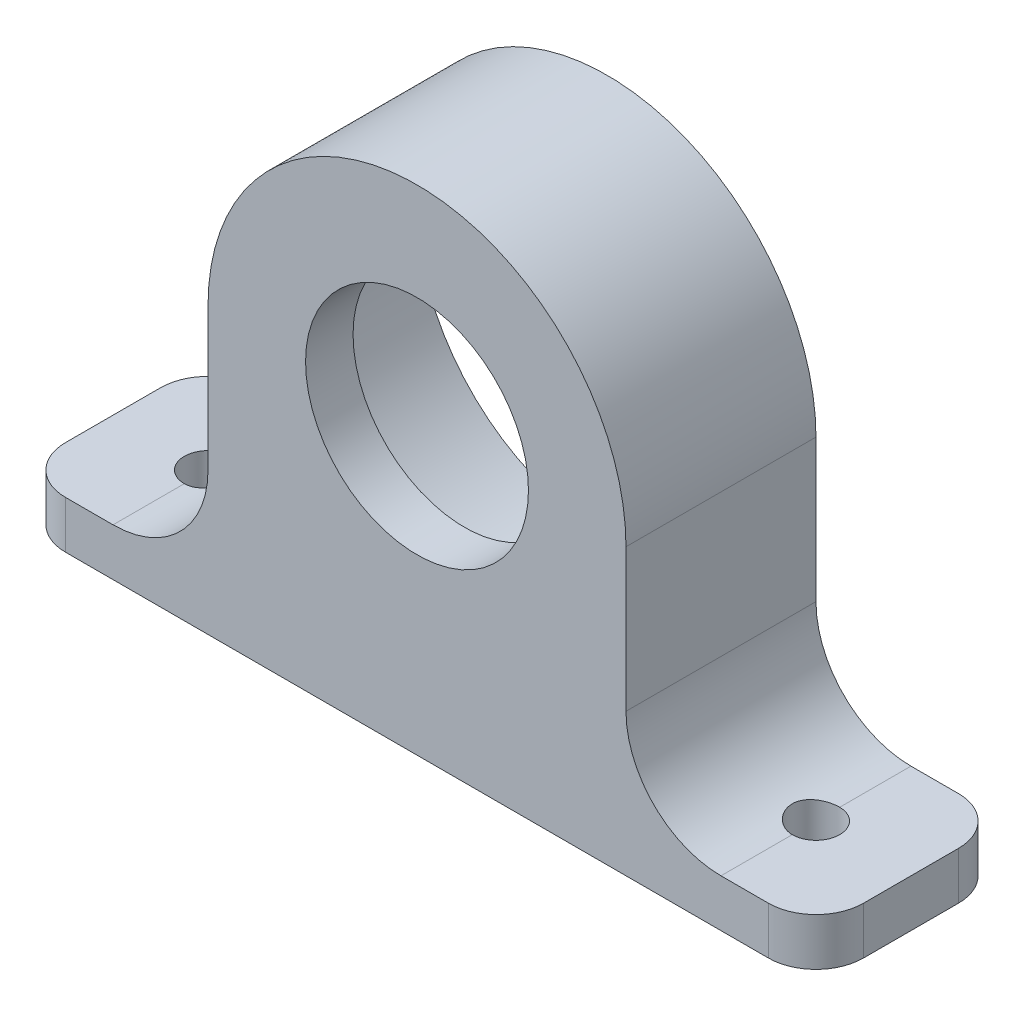
SolidWorks part; units mm, degrees
ref_plane "Plan de face" through (0, 0, 0) normal (0, 0, 1) x (1, 0, 0)
ref_plane "Plan de dessus" through (0, 0, 0) normal (0, 1, 0) x (1, 0, 0)
ref_plane "Plan de droite" through (0, 0, 0) normal (1, 0, 0) x (0, 0, -1)
sketch "Esquisse1" plane through (0, 0, 0) normal (0, 0, 1) x (1, 0, 0)
  line L0 (42, 0) -> (-42, 0)
  line L1 (-42, 0) -> (-42, 5)
  line L2 (-42, 5) -> (-22, 5)
  line L3 (-22, 5) -> (-22, 30)
  line L4 (0, 11.6708) -> (0, 4.3779) construction
  line L5 (42, 0) -> (42, 5)
  line L6 (42, 5) -> (22, 5)
  line L7 (22, 5) -> (22, 30)
  arc A2 (-22, 30) -> (22, 30) centre (0, 30) cw
  circle A3 centre (0, 30) radius 20
  point P12 (0, 0)
  dimension "D1" = 22
  dimension "D3" = 40
  dimension "D2" = 30
  dimension "D4" = 20
  dimension "D5" = 5
extrude "Boss.-Extru.1" add sketch "Esquisse1" along normal blind 20
sketch "Esquisse2" plane through (0, 5, 0) normal (0, 1, 0) x (1, 0, 0)
  line L0 (-42, -20) -> (-42, 0) construction
  line L2 (0, 8.854) -> (0, 0) construction
  circle A0 centre (-32, -10) radius 2.5
  circle A2 centre (32, -10) radius 2.5
  point P4 (-42, -10)
  dimension "D1" = 5
  dimension "D2" = 32
extrude "Enlèv. mat.-Extru.1" cut sketch "Esquisse2" against normal blind 15
fillet "Congé1" radius 10 2 edges at (22, 5, 10) (-22, 5, 10)
fillet "Congé2" radius 5 4 edges at (-42, 2.5, 0) (42, 2.5, 0) (42, 2.5, 20) (-42, 2.5, 20)
sketch "Esquisse3" plane through (0, 0, 20) normal (0, 0, 1) x (1, 0, 0)
  circle A0 centre (0, 30) radius 20
  circle A1 centre (0, 30) radius 11.7327
  dimension "D1" = 40
extrude "Boss.-Extru.2" add sketch "Esquisse3" against normal blind 5
